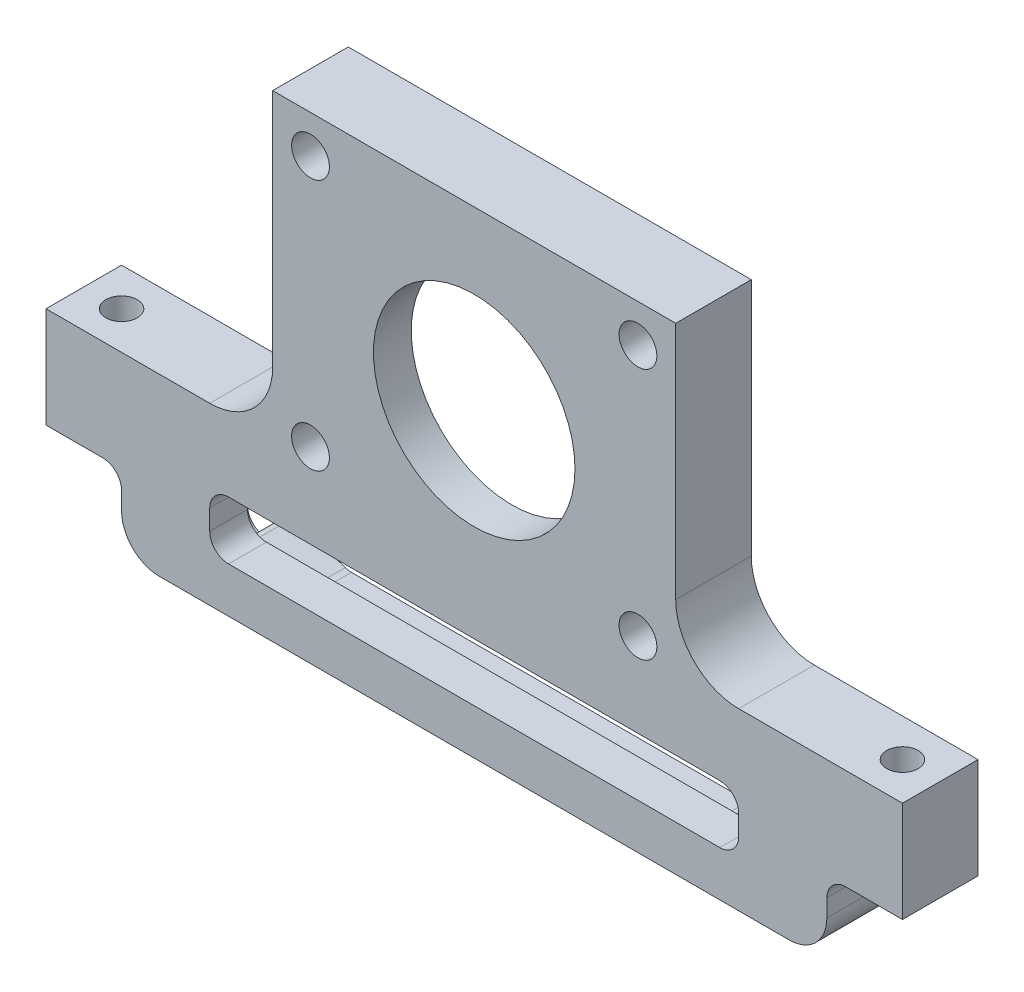
SolidWorks part; units mm, degrees
material "1060 Alloy"
ref_plane "Front Plane" through (0, 0, 0) normal (0, 0, 1) x (1, 0, 0)
ref_plane "Top Plane" through (0, 0, 0) normal (0, 1, 0) x (1, 0, 0)
ref_plane "Right Plane" through (0, 0, 0) normal (1, 0, 0) x (0, 0, -1)
sketch "Sketch1" plane through (0, 0, 0) normal (0, 0, 1) x (1, 0, 0)
  line L0 (0, 0) -> (6, 0)
  line L1 (6, 0) -> (6, -5.9)
  line L2 (6, -5.9) -> (62, -5.9)
  line L3 (62, -5.9) -> (62, 0)
  line L4 (62, 0) -> (68, 0)
  line L5 (68, 0) -> (68, 8)
  line L6 (68, 8) -> (50, 8)
  line L7 (50, 8) -> (50, 32)
  line L8 (50, 32) -> (18, 32)
  line L9 (18, 32) -> (18, 8)
  line L10 (18, 8) -> (0, 8)
  line L11 (0, 8) -> (0, 0)
  line L13 (13, 2.3) -> (55, 2.3)
  line L14 (13, 2.3) -> (13, -2.3)
  line L15 (13, -2.3) -> (55, -2.3)
  line L16 (55, 2.3) -> (55, -2.3)
  circle A0 centre (34, 18) radius 8
  dimension "D12" = 16
  dimension "D1" = 4.6
  dimension "D2" = 32
  dimension "D3" = 32
  dimension "D4" = 15.7
  dimension "D5" = 8
  dimension "D6" = 3.6
  dimension "D9" = 7
  dimension "D10" = 42
  dimension "D11" = 18
  dimension "D13" = 16
  dimension "D14" = 68
  dimension "D15" = 56
extrude "Boss-Extrude1" add sketch "Sketch1" along normal blind 6
sketch "Sketch3" plane through (0, 0, 0) normal (0, 0, -1) x (-1, 0, 0)
  circle A0 centre (-34, 18) radius 13
  dimension "D1" = 26
extrude "Cut-Extrude2" cut sketch "Sketch3" against normal offset from surface (3 mm away) 3 up to face at (34, 0, 6)
hole_wizard "Tap Drill for M3 Tap1" positions "Sketch5" profile "Sketch4" hole size "M3" standard "ISO"
sketch "Sketch5" plane through (53.9899, 0, -7.4052) normal (0, -1, 0) x (-1, 0, 0)
  line L4 (-14.0101, -13.4052) -> (-14.0101, -7.4052) construction
  line L5 (53.9899, -13.4052) -> (53.9899, -7.4052) construction
  line L7 (-8.0101, -13.4052) -> (-14.0101, -13.4052) construction
  point P0 (50.9899, -10.4052)
  point P2 (-11.0101, -10.4052)
  dimension "D1" = 3
  dimension "D2" = 3
  dimension "D3" = 3
sketch "Sketch4" plane through (3, 0, 3) normal (1, 0, 0) x (0, 0, -1)
  line L0 (0, 0) -> (0, 8.7511)
  line L1 (0, 8.7511) -> (1.25, 8)
  line L2 (1.25, 8) -> (1.25, 0)
  line L5 (1.25, 0) -> (0, 0)
  line L10 (0, 8.7511) -> (-1.25, 8) construction
  line L11 (0, -6.35) -> (0, 107.95) construction
  dimension "Hole Dia." = 2.5
  dimension "Hole Depth" = 8
  dimension "Drill Angle" = 118
sketch "Sketch7" plane through (0, 0, 0) normal (0, 0, -1) x (-1, 0, 0)
  line L1 (-58, 4) -> (-10, 4)
  line L2 (-58, 4) -> (-58, -4)
  line L3 (-58, -4) -> (-10, -4)
  line L4 (-10, 4) -> (-10, -4)
  line L6 (-55, 2.3) -> (-13, 2.3) construction
  line L8 (-55, -2.3) -> (-55, 2.3) construction
  line L10 (-13, 2.3) -> (-13, -2.3) construction
  dimension "D1" = 3
  dimension "D2" = 8
  dimension "D3" = 1.7
  dimension "D4" = 3
extrude "Cut-Extrude4" cut sketch "Sketch7" against normal blind 3
fillet "Fillet5" radius 1.5 4 edges at (13, -2.3, 4.5) (13, 2.3, 4.5) (55, 2.3, 4.5) (55, -2.3, 4.5)
fillet "Fillet1" radius 2 4 edges at (10, -4, 1.5) (10, 4, 1.5) (58, -4, 1.5) (58, 4, 1.5)
sketch "Sketch8" plane through (0, 0, 6) normal (0, 0, 1) x (1, 0, 0)
  line L0 (18, 32) -> (18, 8) construction
  line L1 (50, 32) -> (18, 32) construction
  line L3 (50, 8) -> (50, 32) construction
  circle A0 centre (21, 29) radius 1.5
  circle A1 centre (47, 29) radius 1.5
  circle A2 centre (47, 9) radius 1.5
  circle A3 centre (21, 9) radius 1.5
  dimension "D1" = 3
  dimension "D2" = 3
  dimension "D3" = 3
  dimension "D4" = 20
  dimension "D5" = 3
extrude "Cut-Extrude5" cut sketch "Sketch8" against normal up to next
fillet "Fillet2" radius 5 2 edges at (50, 8, 3) (18, 8, 3)
fillet "Fillet3" radius 1.5 2 edges at (62, 0, 3) (6, 0, 3)
fillet "Fillet4" radius 3 2 edges at (6, -5.9, 3) (62, -5.9, 3)
sketch "Sketch9" plane through (0, 0, 0) normal (0, 0, -1) x (-1, 0, 0)
  line L1 (-53.5, 2.25) -> (-12.5, 2.25) construction
  line L2 (-53.5, 2.25) -> (-53.5, -2.25) construction
  line L3 (-53.5, -2.25) -> (-12.5, -2.25) construction
  line L4 (-12.5, 2.25) -> (-12.5, -2.25) construction
  line L5 (-58, 5) -> (-55, 5)
  line L6 (-58, 5) -> (-58, -5)
  line L7 (-58, -5) -> (-55, -5)
  line L8 (-55, 5) -> (-55, -5)
  line L9 (-55, 0.8) -> (-55, -0.8) construction
  line L11 (-56, -4) -> (-12, -4) construction
  line L12 (-12, 4) -> (-56, 4) construction
  line L13 (-53.5, -2.3) -> (-14.5, -2.3) construction
  line L14 (-53.9, -2.65) -> (-12.1, -2.65) construction
  line L15 (-12.1, 2.65) -> (-12.1, -2.65) construction
  line L16 (-53.9, 2.65) -> (-12.1, 2.65) construction
  line L17 (-53.9, 2.65) -> (-53.9, -2.65) construction
  line L18 (-58, 2) -> (-58, -2) construction
  dimension "D1" = 41
  dimension "D2" = 4.5
  dimension "D4" = 1.5
  dimension "D5" = 3
  dimension "D6" = 1
  dimension "D7" = 1
  dimension "D8" = 0.05
  dimension "D9" = 0.4
extrude "Cut-Extrude6" cut sketch "Sketch9" against normal up to surface (3 mm away) up to face at (34, 0, 3)
sketch "Sketch10" plane through (0, 0, 0) normal (0, 0, -1) x (-1, 0, 0)
  line L0 (-55, 4) -> (-55, 3)
  line L1 (-54.3392, 2.5266) -> (-50, 4)
  line L2 (-12, 4) -> (-55, 4) construction
  line L3 (-50, 4) -> (-55, 4)
  line L4 (-55, -4) -> (-55, -3)
  line L5 (-54.3392, -2.5266) -> (-50, -4)
  line L6 (-55, -4) -> (-12, -4) construction
  line L7 (-50, -4) -> (-55, -4)
  arc A0 (-55, 3) -> (-54.3392, 2.5266) centre (-54.5, 3) ccw
  arc A1 (-55, -3) -> (-54.3392, -2.5266) centre (-54.5, -3) cw
  dimension "D2" = 0.5
  dimension "D1" = 5
  dimension "D3" = 1
extrude "Boss-Extrude2" add sketch "Sketch10" against normal up to surface (3 mm away) up to face at (37.9172, 0, 3)
fillet "Fillet6" radius 1.5 6 edges at (50, -4, 1.5) (50, 4, 1.5) (55, -5, 1.5) (58, -5, 1.5) (55, 5, 1.5) (58, 5, 1.5)
ref_plane "Plane1" through (34, 0, 0) normal (-1, 0, 0) x (0, 0, 1)
mirror "Mirror1" about plane through (34, 0, 0) normal (-1, 0, 0) of "Fillet6", "Boss-Extrude2", "Cut-Extrude6"
